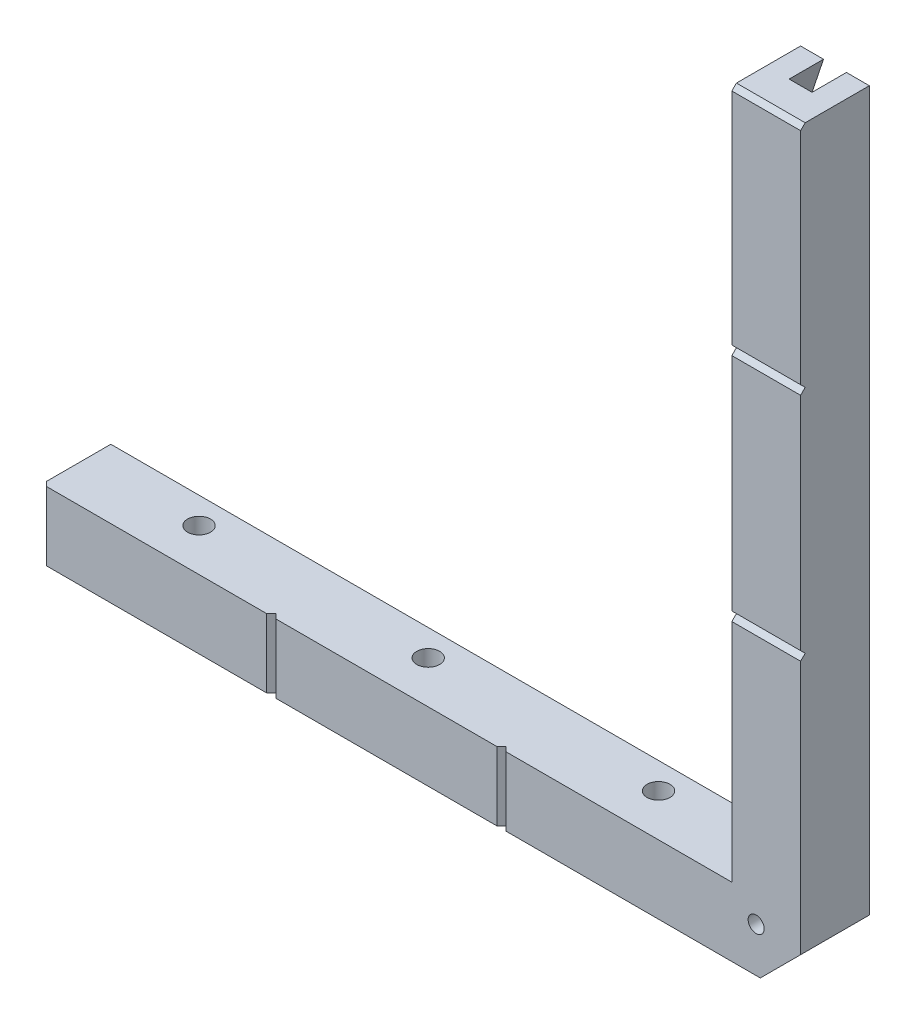
SolidWorks part; units mm, degrees
ref_plane "Front Plane" through (0, 0, 0) normal (0, 0, 1) x (1, 0, 0)
ref_plane "Top Plane" through (0, 0, 0) normal (0, 1, 0) x (1, 0, 0)
ref_plane "Right Plane" through (0, 0, 0) normal (1, 0, 0) x (0, 0, -1)
sketch "Sketch1" plane through (0, 0, 0) normal (0, 0, 1) x (1, 0, 0)
  line L0 (0, 0) -> (0, 150.5)
  line L1 (0, 150.5) -> (15, 150.5)
  line L2 (15, 150.5) -> (15, -15)
  line L3 (15, -15) -> (-150.5, -15)
  line L4 (-150.5, -15) -> (-150.5, 0)
  line L5 (-150.5, 0) -> (0, 0)
  dimension "D1" = 15
  dimension "D2" = 15
  dimension "D3" = 150.5
  dimension "D4" = 150.5
extrude "Body" add sketch "Sketch1" along normal blind 15
sketch "Sketch3" plane through (0, 0, 15) normal (0, 0, 1) x (1, 0, 0)
  line L0 (-150.5, -7.5) -> (15, -7.5) construction
  line L1 (-150.5, 0) -> (-150.5, -15) construction
  line L2 (15, -15) -> (15, 150.5) construction
  line L3 (7.5, 150.5) -> (7.5, -15) construction
  line L4 (15, 150.5) -> (0, 150.5) construction
  line L5 (-150.5, -15) -> (15, -15) construction
  line L6 (0, 0) -> (-150.5, 0) construction
  line L7 (-51.25, -15) -> (-49.25, -15)
  line L8 (-51.25, -15) -> (-51.25, 0)
  line L9 (-51.25, 0) -> (-49.25, 0)
  line L10 (-49.25, -15) -> (-49.25, 0)
  line L11 (-51.25, -15) -> (-49.25, 0) construction
  line L12 (-51.25, 0) -> (-49.25, -15) construction
  line L13 (0, 150.5) -> (0, 0) construction
  line L15 (-101.5, -15) -> (-99.5, -15)
  line L16 (-101.5, -15) -> (-101.5, 0)
  line L17 (-101.5, 0) -> (-99.5, 0)
  line L18 (-99.5, -15) -> (-99.5, 0)
  line L19 (-101.5, -15) -> (-99.5, 0) construction
  line L20 (-101.5, 0) -> (-99.5, -15) construction
  line L27 (0, 51.25) -> (15, 51.25)
  line L28 (0, 51.25) -> (0, 49.25)
  line L29 (0, 49.25) -> (15, 49.25)
  line L30 (15, 51.25) -> (15, 49.25)
  line L31 (0, 51.25) -> (15, 49.25) construction
  line L32 (0, 49.25) -> (15, 51.25) construction
  line L33 (0, 101.5) -> (15, 101.5)
  line L34 (0, 101.5) -> (0, 99.5)
  line L35 (0, 99.5) -> (15, 99.5)
  line L36 (15, 101.5) -> (15, 99.5)
  line L37 (0, 101.5) -> (15, 99.5) construction
  line L38 (0, 99.5) -> (15, 101.5) construction
  point P12 (-50.25, -7.5)
  point P21 (-100.5, -7.5)
  point P30 (7.5, 50.25)
  point P35 (7.5, 100.5)
  dimension "D1" = 2
  dimension "D2" = 50.25
  dimension "D3" = 100.5
  dimension "D5" = 2
  dimension "D7" = 2
  dimension "D8" = 100.5
  dimension "D9" = 50.25
  dimension "D10" = 2
extrude "Field Cut" cut sketch "Sketch3" against normal blind 2
fillet "Field Chamfer" radius 2 8 edges at (-101.5, -7.5, 13) (-99.5, -7.5, 13) (-51.25, -7.5, 13) (-49.25, -7.5, 13) (7.5, 49.25, 13) (7.5, 51.25, 13) (7.5, 101.5, 13) (7.5, 99.5, 13) profile chamfer
sketch "Sketch4" plane through (0, -15, 0) normal (0, -1, 0) x (1, 0, 0)
  line L0 (-150.5, 15) -> (-150.5, 14)
  line L1 (-150.5, 15) -> (-150.5, 0) construction
  line L2 (-150.5, 14) -> (-149.5, 15)
  line L3 (-150.5, 15) -> (-101.5, 15) construction
  line L4 (-149.5, 15) -> (-150.5, 15)
  dimension "D1" = 1
  dimension "D2" = 1
extrude "Click Chamfer 1" cut sketch "Sketch4" against normal through all both and the other way through all
sketch "Sketch5" plane through (15, 0, 0) normal (1, 0, 0) x (0, 0, -1)
  line L0 (-15, 150.5) -> (-15, 149.5)
  line L1 (-15, 101.5) -> (-15, 150.5) construction
  line L2 (-15, 149.5) -> (-14, 150.5)
  line L3 (-15, 150.5) -> (0, 150.5) construction
  line L4 (-14, 150.5) -> (-15, 150.5)
  dimension "D1" = 1
  dimension "D2" = 1
extrude "Click Chamfer 2" cut sketch "Sketch5" against normal through all both and the other way through all
sketch "Sketch7" plane through (0, 0, 0) normal (-1, 0, 0) x (0, 0, 1)
  line L0 (5.75, 150.5) -> (5.75, -15) construction
  line L3 (14, 150.5) -> (0, 150.5) construction
  line L4 (14, -15) -> (0, -15) construction
  line L5 (0, 150.5) -> (0, 0) construction
  circle A0 centre (5.75, 75.25) radius 2.5
  circle A1 centre (5.75, 125.5) radius 2.5
  circle A2 centre (5.75, 25.25) radius 2.5
  dimension "D2" = 5
  dimension "D4" = 5
  dimension "D6" = 5
  dimension "D1" = 25
  dimension "D3" = 25
  dimension "D5" = 25
  dimension "D7" = 5.75
  dimension "D8" = 0
  dimension "D9" = 0
  dimension "D10" = 0
extrude "LED Hole 2" cut sketch "Sketch7" against normal blind 8
sketch "Sketch8" plane through (0, 0, 0) normal (0, 1, 0) x (1, 0, 0)
  line L0 (-150.5, -5.75) -> (0, -5.75) construction
  line L1 (-150.5, -14) -> (-150.5, 0) construction
  line L2 (0, -15) -> (0, 0) construction
  line L3 (0, 0) -> (-150.5, 0) construction
  circle A0 centre (-125.5, -5.75) radius 2.5
  circle A1 centre (-75.5, -5.75) radius 2.5
  circle A2 centre (-25.25, -5.75) radius 2.5
  dimension "D3" = 5
  dimension "D4" = 5
  dimension "D5" = 5
  dimension "D1" = 5.75
  dimension "D2" = 25
  dimension "D6" = 25
  dimension "D7" = 25
extrude "LED Hole 1" cut sketch "Sketch8" against normal blind 8
sketch "Sketch9" plane through (0, 0, 15) normal (0, 0, 1) x (1, 0, 0)
  line L0 (15, -6.2132) -> (6.2132, -15)
  line L1 (15, -15) -> (15, 49.25) construction
  line L2 (-49.25, -15) -> (15, -15) construction
  line L3 (6.2132, -15) -> (15, -15)
  line L4 (15, -15) -> (15, -6.2132)
  dimension "D1" = 15
extrude "Corner Chamfer" cut sketch "Sketch9" against normal through all both and the other way through all
sketch "Sketch10" plane through (0, 0, 0) normal (0, 0, -1) x (-1, 0, 0)
  line L0 (150.5, -7.5) -> (129.292, -7.5) construction
  line L1 (150.5, 0) -> (150.5, -15) construction
  line L2 (150.5, -5) -> (143, -2.5)
  line L3 (143, -2.5) -> (143, -12.5)
  line L4 (143, -12.5) -> (150.5, -10)
  line L5 (150.5, -10) -> (150.5, -5)
  line L6 (-7.5, 150.5) -> (-7.5, 137.0187) construction
  line L7 (-15, 150.5) -> (0, 150.5) construction
  line L8 (-7.5, 150.5) -> (-10, 150.5)
  line L9 (-10, 150.5) -> (-12.5, 143)
  line L10 (-12.5, 143) -> (-7.5, 143)
  line L11 (-7.5, 143) -> (-2.5, 143)
  line L12 (-2.5, 143) -> (-5, 150.5)
  line L13 (-5, 150.5) -> (-7.5, 150.5)
  dimension "D1" = 2.5
  dimension "D2" = 2.5
  dimension "D3" = 5
  dimension "D4" = 5
  dimension "D5" = 2.5
  dimension "D6" = 2.5
  dimension "D7" = 5
  dimension "D8" = 5
  dimension "D9" = 7.5
  dimension "D10" = 7.5
extrude "Click Hole" cut sketch "Sketch10" against normal blind 7.5
ref_plane "Plane1" through (0, -1, 0) normal (0, 1, 0) x (1, 0, 0)
sketch "Sketch12" plane through (0, -1, 0) normal (0, 1, 0) x (1, 0, 0)
  line L0 (-25.25, -5.75) -> (-139.8208, -5.75) construction
  line L1 (-125.5, -5.75) -> (-125.5, -15) construction
  line L2 (-35.75, -13.25) -> (-34.75, -13.25)
  line L3 (-35.75, -13.25) -> (-35.75, 1.75)
  line L4 (-35.75, 1.75) -> (-34.75, 1.75)
  line L5 (-34.75, -13.25) -> (-34.75, 1.75)
  line L6 (-35.75, -13.25) -> (-34.75, 1.75) construction
  line L7 (-35.75, 1.75) -> (-34.75, -13.25) construction
  line L8 (-15.75, -13.25) -> (-14.75, -13.25)
  line L9 (-15.75, -13.25) -> (-15.75, 1.75)
  line L10 (-15.75, 1.75) -> (-14.75, 1.75)
  line L11 (-14.75, -13.25) -> (-14.75, 1.75)
  line L12 (-15.75, -13.25) -> (-14.75, 1.75) construction
  line L13 (-15.75, 1.75) -> (-14.75, -13.25) construction
  line L14 (-66, -13.25) -> (-65, -13.25)
  line L15 (-66, -13.25) -> (-66, 1.75)
  line L16 (-66, 1.75) -> (-65, 1.75)
  line L17 (-65, -13.25) -> (-65, 1.75)
  line L18 (-66, -13.25) -> (-65, 1.75) construction
  line L19 (-66, 1.75) -> (-65, -13.25) construction
  line L20 (-86, -13.25) -> (-85, -13.25)
  line L21 (-86, -13.25) -> (-86, 1.75)
  line L22 (-86, 1.75) -> (-85, 1.75)
  line L23 (-85, -13.25) -> (-85, 1.75)
  line L24 (-86, -13.25) -> (-85, 1.75) construction
  line L25 (-86, 1.75) -> (-85, -13.25) construction
  line L26 (-116, -13.25) -> (-115, -13.25)
  line L27 (-116, -13.25) -> (-116, 1.75)
  line L28 (-116, 1.75) -> (-115, 1.75)
  line L29 (-115, -13.25) -> (-115, 1.75)
  line L30 (-116, -13.25) -> (-115, 1.75) construction
  line L31 (-116, 1.75) -> (-115, -13.25) construction
  line L32 (-136, -13.25) -> (-135, -13.25)
  line L33 (-136, -13.25) -> (-136, 1.75)
  line L34 (-136, 1.75) -> (-135, 1.75)
  line L35 (-135, -13.25) -> (-135, 1.75)
  line L36 (-136, -13.25) -> (-135, 1.75) construction
  line L37 (-136, 1.75) -> (-135, -13.25) construction
  line L38 (-101.5, -15) -> (-149.5, -15) construction
  line L39 (-75.5, -5.75) -> (-75.5, 0) construction
  line L40 (0, 0) -> (-150.5, 0) construction
  line L41 (-25.25, -5.75) -> (-25.25, -15) construction
  line L42 (0, -15) -> (-49.25, -15) construction
  point P3 (-35.25, -5.75)
  point P8 (-15.25, -5.75)
  point P13 (-65.5, -5.75)
  point P18 (-85.5, -5.75)
  point P23 (-115.5, -5.75)
  point P28 (-135.5, -5.75)
  dimension "D1" = 1
  dimension "D2" = 1
  dimension "D3" = 1
  dimension "D4" = 1
  dimension "D5" = 1
  dimension "D6" = 1
  dimension "D7" = 10
  dimension "D8" = 10
  dimension "D9" = 10
  dimension "D10" = 10
  dimension "D11" = 10
  dimension "D12" = 10
  dimension "D13" = 15
  dimension "D14" = 15
  dimension "D15" = 15
  dimension "D16" = 15
  dimension "D17" = 15
  dimension "D18" = 15
extrude "Light Guide 1" cut sketch "Sketch12" against normal blind 13
ref_plane "Plane2" through (1, 0, 0) normal (-1, 0, 0) x (0, 0, 1)
sketch "Sketch13" plane through (1, 0, 0) normal (-1, 0, 0) x (0, 0, 1)
  line L0 (5.75, 125.5) -> (5.75, 25.25) construction
  line L1 (5.75, 25.25) -> (5.75, 15.7929) construction
  line L2 (5.75, 75.25) -> (0, 75.25) construction
  line L3 (-1.75, 35.75) -> (13.25, 35.75)
  line L4 (-1.75, 35.75) -> (-1.75, 34.75)
  line L5 (-1.75, 34.75) -> (13.25, 34.75)
  line L6 (13.25, 35.75) -> (13.25, 34.75)
  line L7 (-1.75, 35.75) -> (13.25, 34.75) construction
  line L8 (-1.75, 34.75) -> (13.25, 35.75) construction
  line L9 (-1.75, 15.75) -> (13.25, 15.75)
  line L10 (-1.75, 15.75) -> (-1.75, 14.75)
  line L11 (-1.75, 14.75) -> (13.25, 14.75)
  line L12 (13.25, 15.75) -> (13.25, 14.75)
  line L13 (-1.75, 15.75) -> (13.25, 14.75) construction
  line L14 (-1.75, 14.75) -> (13.25, 15.75) construction
  line L15 (-1.75, 65.75) -> (13.25, 65.75)
  line L16 (-1.75, 65.75) -> (-1.75, 64.75)
  line L17 (-1.75, 64.75) -> (13.25, 64.75)
  line L18 (13.25, 65.75) -> (13.25, 64.75)
  line L19 (-1.75, 65.75) -> (13.25, 64.75) construction
  line L20 (-1.75, 64.75) -> (13.25, 65.75) construction
  line L21 (-1.75, 85.75) -> (13.25, 85.75)
  line L22 (-1.75, 85.75) -> (-1.75, 84.75)
  line L23 (-1.75, 84.75) -> (13.25, 84.75)
  line L24 (13.25, 85.75) -> (13.25, 84.75)
  line L25 (-1.75, 85.75) -> (13.25, 84.75) construction
  line L26 (-1.75, 84.75) -> (13.25, 85.75) construction
  line L27 (-1.75, 116) -> (13.25, 116)
  line L28 (-1.75, 116) -> (-1.75, 115)
  line L29 (-1.75, 115) -> (13.25, 115)
  line L30 (13.25, 116) -> (13.25, 115)
  line L31 (-1.75, 116) -> (13.25, 115) construction
  line L32 (-1.75, 115) -> (13.25, 116) construction
  line L33 (-1.75, 135) -> (13.25, 135)
  line L34 (-1.75, 135) -> (-1.75, 136)
  line L35 (-1.75, 136) -> (13.25, 136)
  line L36 (13.25, 135) -> (13.25, 136)
  line L37 (-1.75, 135) -> (13.25, 136) construction
  line L38 (-1.75, 136) -> (13.25, 135) construction
  line L39 (0, 150.5) -> (0, 0) construction
  point P4 (5.75, 35.25)
  point P10 (5.75, 15.25)
  point P15 (5.75, 65.25)
  point P20 (5.75, 85.25)
  point P25 (5.75, 115.5)
  point P30 (5.75, 135.5)
  dimension "D1" = 1
  dimension "D2" = 10
  dimension "D3" = 15
  dimension "D4" = 1
  dimension "D5" = 10
  dimension "D6" = 15
  dimension "D7" = 15
  dimension "D8" = 1
  dimension "D9" = 10
  dimension "D10" = 10
  dimension "D11" = 1
  dimension "D12" = 15
  dimension "D13" = 10
  dimension "D14" = 1
  dimension "D15" = 15
  dimension "D16" = 10
  dimension "D17" = 1
  dimension "D18" = 15
extrude "Light Guide 2" cut sketch "Sketch13" against normal blind 13
sketch "Sketch14" plane through (0, 0, 15) normal (0, 0, 1) x (1, 0, 0)
  line L0 (0, 0) -> (10.6066, -10.6066) construction
  line L1 (15, -6.2132) -> (6.2132, -15) construction
  circle A0 centre (5.3033, -5.3033) radius 1.75
  dimension "D1" = 3.5
extrude "Mounting Hole" cut sketch "Sketch14" against normal through all both and the other way through all
sketch "Sketch15" plane through (0, 0, 0) normal (0, 0, -1) x (-1, 0, 0)
  line L0 (-14, 116) -> (-1, 116) construction
  line L1 (-14, 135) -> (-13, 135)
  line L2 (-14, 135) -> (-14, 116)
  line L3 (-14, 116) -> (-13, 116)
  line L4 (-13, 135) -> (-13, 116)
  line L5 (-14, 65.75) -> (-1, 65.75) construction
  line L6 (-14, 84.75) -> (-13, 84.75)
  line L7 (-14, 84.75) -> (-14, 65.75)
  line L8 (-14, 65.75) -> (-13, 65.75)
  line L9 (-13, 84.75) -> (-13, 65.75)
  line L10 (-14, 15.75) -> (-1, 15.75) construction
  line L11 (-14, 34.75) -> (-13, 34.75)
  line L12 (-14, 34.75) -> (-14, 15.75)
  line L13 (-14, 15.75) -> (-13, 15.75)
  line L14 (-13, 34.75) -> (-13, 15.75)
  line L15 (34.75, -14) -> (34.75, -1) construction
  line L16 (15.75, -14) -> (34.75, -14)
  line L17 (15.75, -14) -> (15.75, -13)
  line L18 (15.75, -13) -> (34.75, -13)
  line L19 (34.75, -14) -> (34.75, -13)
  line L20 (85, -14) -> (85, -1) construction
  line L21 (66, -14) -> (85, -14)
  line L22 (66, -14) -> (66, -13)
  line L23 (66, -13) -> (85, -13)
  line L24 (85, -14) -> (85, -13)
  line L25 (135, -14) -> (135, -1) construction
  line L26 (116, -14) -> (135, -14)
  line L27 (116, -14) -> (116, -13)
  line L28 (116, -13) -> (135, -13)
  line L29 (135, -14) -> (135, -13)
  dimension "D1" = 1
  dimension "D2" = 1
  dimension "D3" = 1
  dimension "D4" = 1
  dimension "D5" = 1
  dimension "D6" = 1
extrude "Cut-Extrude1" cut sketch "Sketch15" against normal blind 13.25
